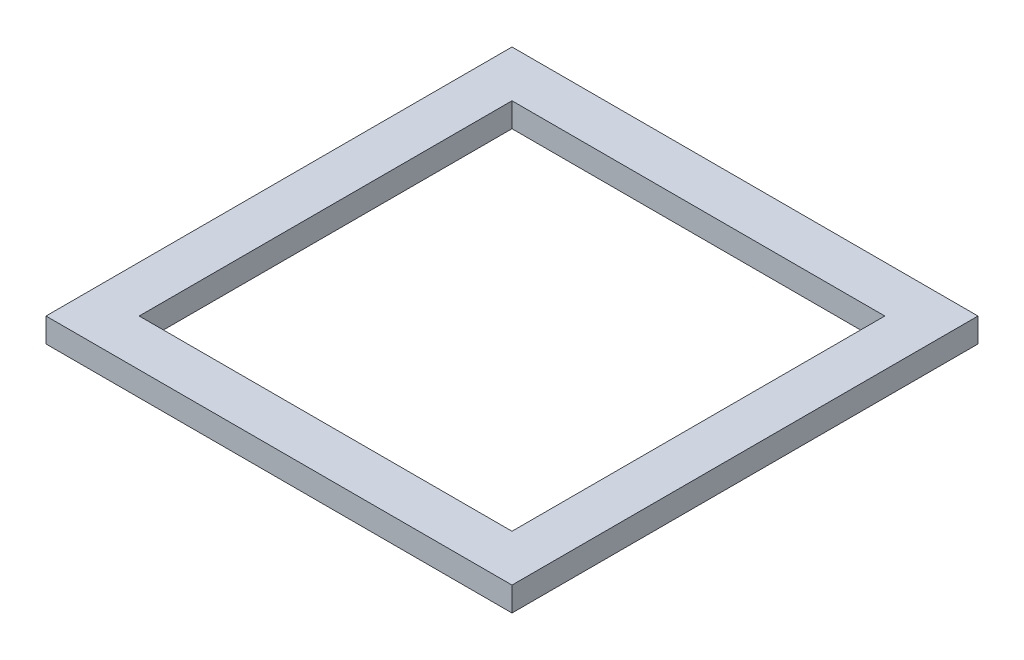
SolidWorks part; units mm, degrees
ref_plane "Front Plane" through (0, 0, 0) normal (0, 0, 1) x (1, 0, 0)
ref_plane "Top Plane" through (0, 0, 0) normal (0, 1, 0) x (1, 0, 0)
ref_plane "Right Plane" through (0, 0, 0) normal (1, 0, 0) x (0, 0, -1)
sketch "Sketch1" plane through (0, 0, 0) normal (0, 1, 0) x (1, 0, 0)
  line L0 (0, 44.45) -> (0, -44.45) construction
  line L1 (-25.4, -25.4) -> (25.4, -25.4)
  line L2 (-25.4, -25.4) -> (-25.4, 25.4)
  line L3 (-25.4, 25.4) -> (25.4, 25.4)
  line L4 (25.4, -25.4) -> (25.4, 25.4)
  line L5 (-25.4, -25.4) -> (25.4, 25.4) construction
  line L6 (-25.4, 25.4) -> (25.4, -25.4) construction
  line L7 (31.75, -31.75) -> (-31.75, -31.75)
  line L8 (31.75, -31.75) -> (31.75, 31.75)
  line L9 (31.75, 31.75) -> (-31.75, 31.75)
  line L10 (-31.75, -31.75) -> (-31.75, 31.75)
  line L11 (31.75, -31.75) -> (-31.75, 31.75) construction
  line L12 (31.75, 31.75) -> (-31.75, -31.75) construction
  line L13 (44.45, -44.45) -> (-44.45, -44.45)
  line L14 (44.45, -44.45) -> (44.45, 44.45)
  line L15 (44.45, 44.45) -> (-44.45, 44.45)
  line L16 (-44.45, -44.45) -> (-44.45, 44.45)
  line L17 (44.45, -44.45) -> (-44.45, 44.45) construction
  line L18 (44.45, 44.45) -> (-44.45, -44.45) construction
  line L19 (-44.45, 0) -> (44.45, 0) construction
  circle A0 centre (-38.1, 38.1) radius 2.032
  circle A1 centre (38.1, 38.1) radius 2.032
  circle A2 centre (38.1, -38.1) radius 2.032
  circle A3 centre (-38.1, -38.1) radius 2.032
  point P0 (0, 0)
  point P6 (0, 0)
  point P11 (0, 0)
  dimension "D7" = 4.064
  dimension "D1" = 50.8
  dimension "D2" = 50.8
  dimension "D3" = 6.35
  dimension "D4" = 6.35
  dimension "D5" = 12.7
  dimension "D6" = 12.7
  dimension "D8" = 6.35
extrude "Boss-Extrude2" add sketch "Sketch1" along normal blind 3.175 contours L16 L13 L14 L15 A1 A0 L7 L10 L9 L8 A2 A3 | L1 L4 L3 L2 | L10 L7 L8 L9 L4 L1 L2 L3 region at (0, 0, 0) region at (0, 0, 30.852) region at (0, 0, 43.1928)
extrude "Boss-Extrude3" add sketch "Sketch1<4>" along normal blind 3.302 from surface contours L7 L10 L9 L8 | L1 L4 L3 L2 starting at face at (38.1, 3.175, -36.068)
sketch "Sketch1<4>" plane through (0, 0, 0) normal (0, 1, 0) x (1, 0, 0) same geometry as "Sketch1"
sketch "Sketch2" plane through (0, 3.175, 0) normal (0, 1, 0) x (1, 0, 0)
  line L1 (44.45, -44.45) -> (-44.45, -44.45)
  line L2 (44.45, -44.45) -> (44.45, 44.45)
  line L3 (44.45, 44.45) -> (-44.45, 44.45)
  line L4 (-44.45, -44.45) -> (-44.45, 44.45)
extrude "Cut-Extrude1" cut sketch "Sketch2" against normal through all
equation "\"D1@Boss-Extrude2\"=1/8in"
equation "\"D1@Boss-Extrude3\"=2/8in"
